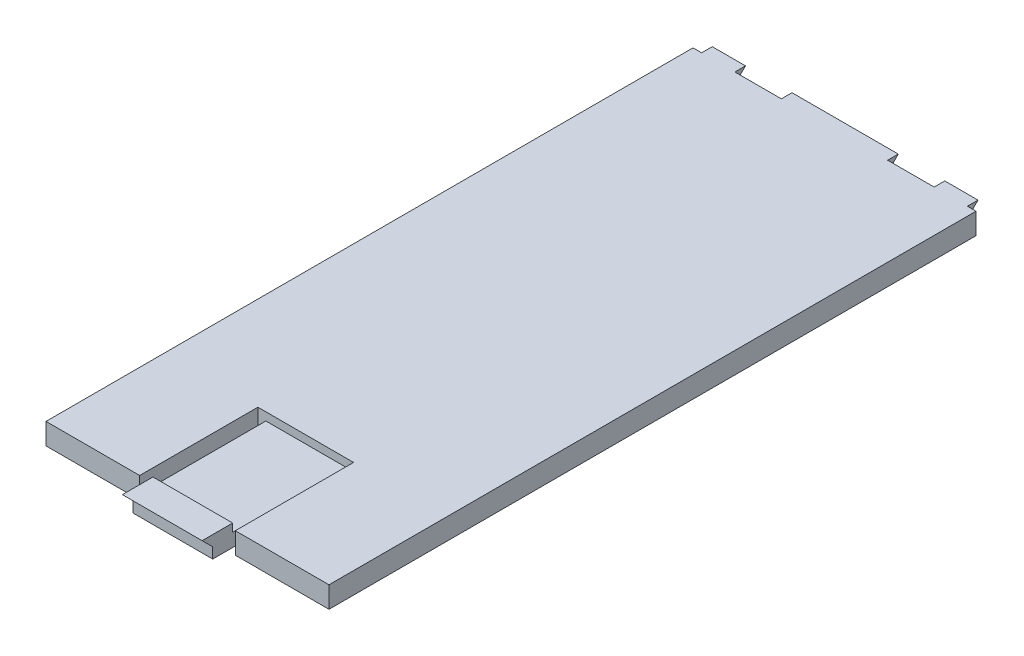
SolidWorks part; units mm, degrees
ref_plane "Front Plane" through (0, 0, 0) normal (0, 0, 1) x (1, 0, 0)
ref_plane "Top Plane" through (0, 0, 0) normal (0, 1, 0) x (1, 0, 0)
ref_plane "Right Plane" through (0, 0, 0) normal (1, 0, 0) x (0, 0, -1)
sketch "Door Plate 1.6 Sketch" plane through (0, 0, 0) normal (0, 1, 0) x (1, 0, 0)
  line L0 (9.35, 16.2) -> (17, 16.2)
  line L1 (17, 16.2) -> (17, 15.1)
  line L2 (17, 15.1) -> (23, 15.1)
  line L3 (23, 15.1) -> (23, 16.2)
  line L4 (23, 16.2) -> (30.65, 16.2)
  line L5 (30.65, 16.2) -> (30.65, 64.9)
  line L6 (30.65, 64.9) -> (9.35, 64.9)
  line L7 (9.35, 64.9) -> (9.35, 16.2)
extrude "Door Plate 1.6" add sketch "Door Plate 1.6 Sketch" along normal blind 1.6
sketch "Latch Finger Slots 0.6 Sketch" plane through (0, 0, 0) normal (0, 1, 0) x (1, 0, 0)
  line L0 (16.4, 16.2) -> (17, 16.2)
  line L1 (17, 16.2) -> (17, 25.1)
  line L2 (17, 25.1) -> (16.4, 25.1)
  line L3 (16.4, 25.1) -> (16.4, 16.2)
  line L4 (23, 16.2) -> (23.6, 16.2)
  line L5 (23.6, 16.2) -> (23.6, 25.1)
  line L6 (23.6, 25.1) -> (23, 25.1)
  line L7 (23, 25.1) -> (23, 16.2)
extrude "Latch Finger Slots 0.6" cut sketch "Latch Finger Slots 0.6 Sketch" along normal blind 1.6
ref_plane "Finger Thin Plane y1.0" through (0, 1, 0) normal (0, 1, 0) x (1, 0, 0)
sketch "Latch Finger Thinning to 1.0 Sketch" plane through (0, 1, 0) normal (0, 1, 0) x (1, 0, 0)
  line L0 (17, 16.6) -> (23, 16.6)
  line L1 (23, 16.6) -> (23, 25.1)
  line L2 (23, 25.1) -> (17, 25.1)
  line L3 (17, 25.1) -> (17, 16.6)
extrude "Latch Finger Thinning to 1.0" cut sketch "Latch Finger Thinning to 1.0 Sketch" along normal blind 0.6
sketch "Far Tongue Strip 45deg Sketch" plane through (0, 0, 0) normal (1, 0, 0) x (0, 0, -1)
  line L0 (64.9, 0.8) -> (64.9, 1.6)
  line L1 (64.9, 1.6) -> (65.7, 1.6)
  line L2 (65.7, 1.6) -> (64.9, 0.8)
extrude "Far Tongue Strip 45deg" add sketch "Far Tongue Strip 45deg Sketch" along normal blind 40
sketch "Latch Hook Strip 45deg Sketch" plane through (0, 0, 0) normal (1, 0, 0) x (0, 0, -1)
  line L0 (15.1, 0.8) -> (15.1, 1.6)
  line L1 (15.1, 1.6) -> (14.3, 1.6)
  line L2 (14.3, 1.6) -> (15.1, 0.8)
extrude "Latch Hook Strip 45deg" add sketch "Latch Hook Strip 45deg Sketch" along normal blind 40
sketch "Tongue + Hook Trim Sketch" plane through (0, 0, 0) normal (0, 1, 0) x (1, 0, 0)
  line L0 (-1, 64.9) -> (10, 64.9)
  line L1 (10, 64.9) -> (10, 65.8)
  line L2 (10, 65.8) -> (-1, 65.8)
  line L3 (-1, 65.8) -> (-1, 64.9)
  line L4 (12.5, 64.9) -> (16, 64.9)
  line L5 (16, 64.9) -> (16, 65.8)
  line L6 (16, 65.8) -> (12.5, 65.8)
  line L7 (12.5, 65.8) -> (12.5, 64.9)
  line L8 (24, 64.9) -> (27.5, 64.9)
  line L9 (27.5, 64.9) -> (27.5, 65.8)
  line L10 (27.5, 65.8) -> (24, 65.8)
  line L11 (24, 65.8) -> (24, 64.9)
  line L12 (30, 64.9) -> (41, 64.9)
  line L13 (41, 64.9) -> (41, 65.8)
  line L14 (41, 65.8) -> (30, 65.8)
  line L15 (30, 65.8) -> (30, 64.9)
  line L16 (-1, 14.2) -> (17, 14.2)
  line L17 (17, 14.2) -> (17, 15.1)
  line L18 (17, 15.1) -> (-1, 15.1)
  line L19 (-1, 15.1) -> (-1, 14.2)
  line L20 (23, 14.2) -> (41, 14.2)
  line L21 (41, 14.2) -> (41, 15.1)
  line L22 (41, 15.1) -> (23, 15.1)
  line L23 (23, 15.1) -> (23, 14.2)
extrude "Tongue + Hook Trim" cut sketch "Tongue + Hook Trim Sketch" along normal through all
